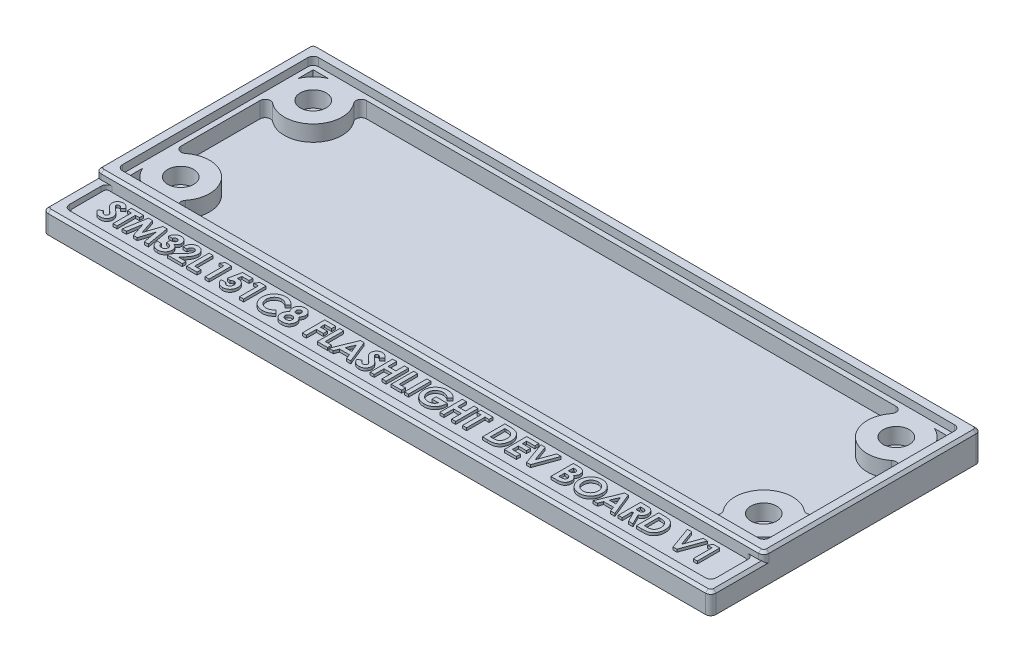
SolidWorks part; units mm, degrees
material "PET"
ref_plane "Front Plane" through (0, 0, 0) normal (0, 0, 1) x (1, 0, 0)
ref_plane "Top Plane" through (0, 0, 0) normal (0, 1, 0) x (1, 0, 0)
ref_plane "Right Plane" through (0, 0, 0) normal (1, 0, 0) x (0, 0, -1)
sketch "base_sketch" plane through (0, 0, 0) normal (0, 1, 0) x (1, 0, 0)
  line L1 (-55, 12.5) -> (55, 12.5) construction
  line L2 (-55, 12.5) -> (-55, -12.5) construction
  line L3 (-55, -12.5) -> (55, -12.5) construction
  line L4 (55, 12.5) -> (55, -12.5) construction
  line L5 (-55, 12.5) -> (55, -12.5) construction
  line L6 (-55, -12.5) -> (55, 12.5) construction
  line L7 (-60.5, 18) -> (60.5, 18) construction
  line L8 (-60.5, 18) -> (-60.5, -18) construction
  line L9 (-60.5, -18) -> (60.5, -18) construction
  line L10 (60.5, 18) -> (60.5, -18) construction
  line L11 (-60.5, 18) -> (60.5, -18) construction
  line L12 (-60.5, -18) -> (60.5, 18) construction
  circle A0 centre (-55, 12.5) radius 2.45 construction
  circle A1 centre (55, 12.5) radius 2.45 construction
  circle A2 centre (-55, -12.5) radius 2.45 construction
  circle A3 centre (55, -12.5) radius 2.45 construction
  point P0 (0, 0)
  point P11 (0, 0)
  dimension "D1" = 4.9
  dimension "D2" = 110
  dimension "D3" = 121
  dimension "D4" = 36
  dimension "D5" = 25
sketch "Sketch3" plane through (0, 0, 0) normal (0, 1, 0) x (1, 0, 0)
  line L14 (-60, -17.5) -> (60, -17.5)
  line L15 (60, -17.5) -> (60, 17.5)
  line L16 (60, 17.5) -> (-60, 17.5)
  line L17 (-60, 17.5) -> (-60, -17.5)
  line L18 (-60, -17.5) -> (60, -17.5)
  line L19 (60, -17.5) -> (60, 17.5)
  line L20 (60, 17.5) -> (-60, 17.5)
  line L21 (-60, 17.5) -> (-60, -17.5)
  line L28 (-63, 20.5) -> (-63, -20.5)
  line L29 (-63, -20.5) -> (63, -20.5)
  line L30 (63, -20.5) -> (63, 20.5)
  line L31 (63, 20.5) -> (-63, 20.5)
  line L32 (-61, -18.5) -> (61, -18.5)
  line L33 (61, -18.5) -> (61, 18.5)
  line L34 (61, 18.5) -> (-61, 18.5)
  line L35 (-61, 18.5) -> (-61, -18.5)
  line L36 (-61, -18.5) -> (61, -18.5)
  line L37 (61, -18.5) -> (61, 18.5)
  line L38 (61, 18.5) -> (-61, 18.5)
  line L39 (-61, 18.5) -> (-61, -18.5)
  line L40 (-63, -20.5) -> (-63, -30.5)
  line L41 (-63, -30.5) -> (63, -30.5)
  line L42 (63, -30.5) -> (63, -20.5)
  line L43 (-61, -20.5) -> (-61, -28.5)
  line L44 (-61, -28.5) -> (61, -28.5)
  line L45 (61, -28.5) -> (61, -20.5)
  dimension "D4" = 10
  dimension "D1" = 0.5
  dimension "D2" = 0.5
  dimension "D3" = 2
  dimension "D5" = 2
extrude "Boss-Extrude1" add sketch "Sketch3" along normal blind 1 contours L38 L39 L36 L37 L21 L20 L19 L18 | L20 L21 L18 L19 | L30 L31 L28 L29 L39 L38 L37 L36 | L45 L44 L43 L29 L40 L41 L42 | L44 L45 L29 L43 region at (0, 0, 0) region at (0, 0, -19.175) region at (0, 0, 28.9366) region at (0, 0, 24.5) region at (-60.8725, 0, 0)
extrude "Boss-Extrude2" add sketch "Sketch3<3>" along normal blind 3 from surface contours L45 L44 L43 L29 L40 L41 L42 | L30 L31 L28 L29 L39 L38 L37 L36 | L38 L39 L36 L37 L21 L20 L19 L18 region at (0, 0, -19.175) region at (0, 0, 28.9366) region at (-60.8725, 0, 0) starting at face at (0, 1, 5)
sketch "Sketch3<3>" plane through (0, 0, 0) normal (0, 1, 0) x (1, 0, 0) same geometry as "Sketch3"
extrude "Boss-Extrude3" add sketch "Sketch3<4>" along normal blind 1.5 from surface contours L30 L31 L28 L29 L39 L38 L37 L36 region at (0, 0, -19.175) starting at face at (0, 4, 0)
sketch "Sketch3<4>" plane through (0, 0, 0) normal (0, 1, 0) x (1, 0, 0) same geometry as "Sketch3"
sketch "Sketch4" plane through (0, 1, 0) normal (0, 1, 0) x (1, 0, 0)
  line L4 (60, 17.5) -> (-60, 17.5)
  line L5 (-60, 17.5) -> (-60, -17.5)
  line L6 (-60, -17.5) -> (60, -17.5)
  line L7 (60, -17.5) -> (60, 17.5)
  line L8 (60, 17.5) -> (-60, 17.5)
  line L9 (-60, 17.5) -> (-60, -17.5)
  line L10 (-60, -17.5) -> (60, -17.5)
  line L11 (60, -17.5) -> (60, 17.5)
  circle A0 centre (-55, -12.5) radius 2.45 construction
  circle A1 centre (55, -12.5) radius 2.45 construction
  circle A2 centre (55, 12.5) radius 2.45 construction
  circle A3 centre (-55, 12.5) radius 2.45 construction
  circle A4 centre (-55, -12.5) radius 2.45
  circle A5 centre (55, -12.5) radius 2.45
  circle A6 centre (55, 12.5) radius 2.45
  circle A7 centre (-55, 12.5) radius 2.45
  circle A8 centre (-55, 12.5) radius 5.45
  circle A9 centre (55, 12.5) radius 5.45
  circle A10 centre (55, -12.5) radius 5.45
  circle A11 centre (-55, -12.5) radius 5.45
  dimension "D1" = 0
  dimension "D2" = 3
extrude "Boss-Extrude4" add sketch "Sketch4" along normal up to surface (3 mm away) contours L8 A8 L9 A7 | L11 A9 L8 A6 | L10 A10 L11 A5 | L10 A11 L9 A4 region at (58.7492, 1, -16.2492) region at (-50.5672, 1, -15.4092) region at (59.8522, 1, 12.5) region at (-55, 1, 17.3522) up to face at (0, 4, 0)
fillet "Fillet1" radius 1 22 edges at (-61, 2.5, 28.5) (61, 2.5, 28.5) (61, 2.5, 20.5) (63, 2, 30.5) (-63, 2, 30.5) (-61, 2.5, 20.5) (-52.8315, 2.5, 17.5) (52.8315, 2.5, 17.5) (60, 2.5, 10.3315) (52.8315, 2.5, -17.5) (-52.8315, 2.5, -17.5) (-60, 2.5, 10.3315) (60, 2.5, -10.3315) (-61, 4.75, 18.5) (61, 4.75, 18.5) (61, 4.75, -18.5) (63, 4.75, 20.5) (-63, 4.75, 20.5) (-63, 2.75, -20.5) (63, 2.75, -20.5) (-61, 4.75, -18.5) (-60, 2.5, -10.3315)
chamfer "Chamfer1" distance 0.5 angle 45 13 edges at (-63, 5.5, 0) (-62.7071, 5.5, 20.2071) (-62.7071, 5.5, -20.2071) (0, 5.5, 20.5) (0, 5.5, -20.5) (62.7071, 5.5, 20.2071) (62.7071, 5.5, -20.2071) (63, 5.5, 0) (-63, 4, 24.5) (-62.7071, 4, 30.2071) (0, 4, 30.5) (62.7071, 4, 30.2071) (63, 4, 24.5)
sketch "Sketch5" plane through (0, 1, 0) normal (0, 1, 0) x (1, 0, 0)
  line L0 (-60.5, -21.5) -> (-60.5, -27.5)
  line L1 (-60, -28) -> (60, -28)
  line L2 (60.5, -27.5) -> (60.5, -21.5)
  line L3 (60, -21) -> (-60, -21)
  line L4 (-61, -21.5) -> (-61, -27.5)
  line L5 (-60, -28.5) -> (60, -28.5)
  line L6 (61, -27.5) -> (61, -21.5)
  line L7 (60, -20.5) -> (-60, -20.5)
  line L8 (-61, -21.5) -> (-61, -27.5) construction
  line L9 (-60, -28.5) -> (60, -28.5) construction
  line L10 (61, -27.5) -> (61, -21.5) construction
  line L11 (60, -20.5) -> (-60, -20.5) construction
  arc A0 (-60.5, -27.5) -> (-60, -28) centre (-60, -27.5) ccw
  arc A1 (60, -28) -> (60.5, -27.5) centre (60, -27.5) ccw
  arc A2 (60.5, -21.5) -> (60, -21) centre (60, -21.5) ccw
  arc A3 (-60, -21) -> (-60.5, -21.5) centre (-60, -21.5) ccw
  arc A4 (-61, -27.5) -> (-60, -28.5) centre (-60, -27.5) ccw
  arc A5 (60, -28.5) -> (61, -27.5) centre (60, -27.5) ccw
  arc A6 (61, -21.5) -> (60, -20.5) centre (60, -21.5) ccw
  arc A7 (-60, -20.5) -> (-61, -21.5) centre (-60, -21.5) ccw
  arc A8 (-61, -27.5) -> (-60, -28.5) centre (-60, -27.5) ccw construction
  arc A9 (60, -28.5) -> (61, -27.5) centre (60, -27.5) ccw construction
  arc A10 (61, -21.5) -> (60, -20.5) centre (60, -21.5) ccw construction
  arc A11 (-60, -20.5) -> (-61, -21.5) centre (-60, -21.5) ccw construction
  dimension "D1" = 0
  dimension "D2" = 0.5
extrude "Boss-Extrude5" add sketch "Sketch5" along normal blind 2 from offset 0.5 separate body
sketch "Sketch6" plane through (0, 3.5, 0) normal (0, 1, 0) x (1, 0, 0)
  line L0 (-60.5, -24.5) -> (60.5, -24.5) construction
  line L1 (-60.5, -27.5) -> (-60.5, -21.5) construction
  line L2 (60.5, -21.5) -> (60.5, -27.5) construction
  line L3 (0, -21) -> (0, -28) construction
  line L4 (-60, -21) -> (60, -21) construction
  line L5 (60, -28) -> (-60, -28) construction
  line L6 (-60.5, -26.5142) -> (60.5, -26.5142) construction
  text T0 "STM32L151C8 FLASHLIGHT DEV BOARD V1" font "Century Gothic" height in points 16
  point P12 (0, -24.5)
extrude "Boss-Extrude6" add sketch "Sketch6" along normal blind 0.5
